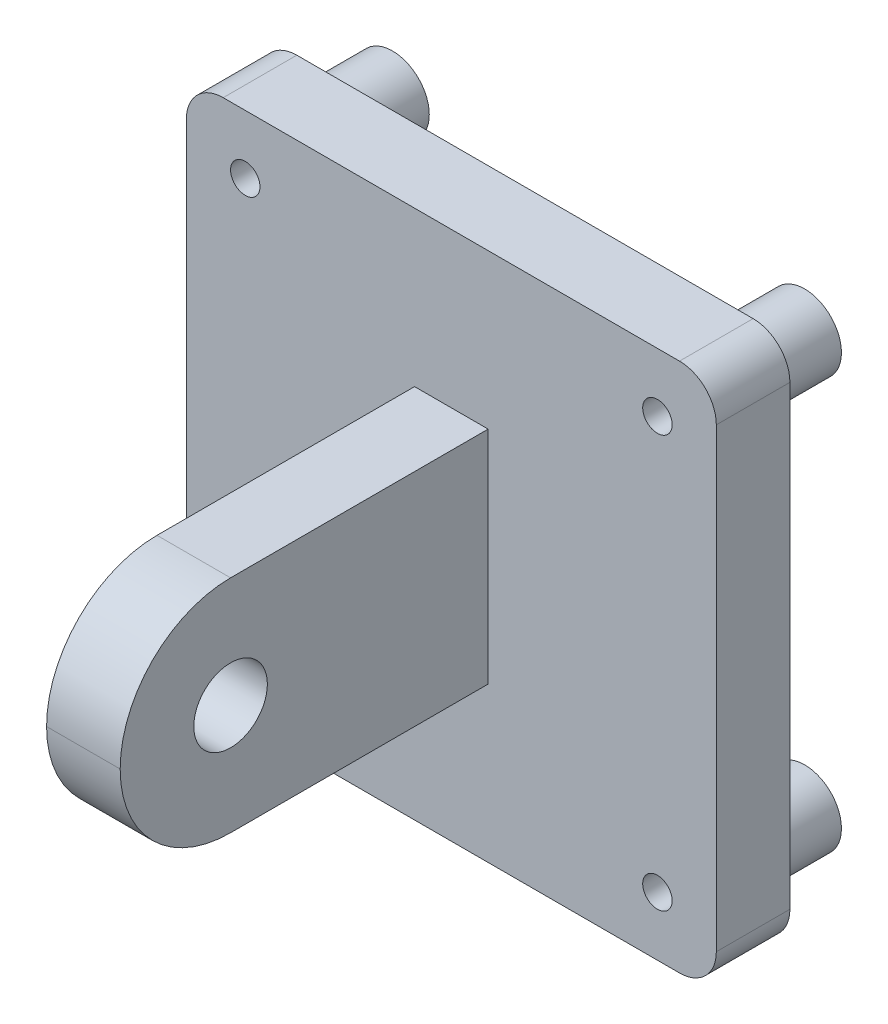
SolidWorks part; units mm, degrees
ref_plane "Front Plane" through (0, 0, 0) normal (0, 0, 1) x (1, 0, 0)
ref_plane "Top Plane" through (0, 0, 0) normal (0, 1, 0) x (1, 0, 0)
ref_plane "Right Plane" through (0, 0, 0) normal (1, 0, 0) x (0, 0, -1)
sketch "Sketch1" plane through (0, 0, 0) normal (0, 0, 1) x (1, 0, 0)
  line L1 (-18, -18) -> (18, -18)
  line L2 (-18, -18) -> (-18, 18)
  line L3 (-18, 18) -> (18, 18)
  line L4 (18, -18) -> (18, 18)
  line L5 (-14, -14) -> (14, -14)
  line L6 (-14, -14) -> (-14, 14)
  line L7 (-14, 14) -> (14, 14)
  line L8 (14, -14) -> (14, 14)
  line L9 (-14, -14) -> (14, 14) construction
  line L10 (-14, 14) -> (14, -14) construction
  circle A0 centre (-14, 14) radius 1
  circle A1 centre (14, 14) radius 1
  circle A2 centre (14, -14) radius 1
  circle A3 centre (-14, -14) radius 1
  circle A4 centre (-14, 14) radius 2.5
  circle A5 centre (14, 14) radius 2.5
  circle A6 centre (14, -14) radius 2.5
  circle A7 centre (-14, -14) radius 2.5
  point P4 (0, 0)
  dimension "D7" = 2
  dimension "D8" = 2
  dimension "D9" = 2
  dimension "D10" = 2
  dimension "D11" = 5
  dimension "D12" = 5
  dimension "D13" = 5
  dimension "D14" = 5
  dimension "D1" = 18
  dimension "D2" = 18
  dimension "D3" = 36
  dimension "D4" = 36
  dimension "D5" = 28
  dimension "D6" = 28
extrude "Boss-Extrude1" add sketch "Sketch1" against normal blind 5 contours L7 A4 L6 A0 | L6 A4 L7 A0 | L8 A5 L7 A1 | L7 A5 L8 A1 | L5 A7 L6 A3 | L6 A7 L5 A3 | L5 A6 L8 A2 | L8 A6 L5 A2 region at (-12.8177, -12.8177, 0) region at (-12.25, -14.0707, 0) region at (12.8177, -12.8177, 0) region at (12.25, -14.0707, 0) region at (-15.7178, 15.7178, 0) region at (-12.8177, 12.8177, 0) region at (12.8177, 12.8177, 0) region at (14.0707, 12.25, 0)
extrude "Boss-Extrude2" add sketch "Sketch1<3>" along normal blind 5 contours L1 L4 L3 L2 A7 L6 A4 L7 A5 L8 A6 L5 | A7 L5 A6 L8 A5 L7 A4 L6 | L6 A7 L5 A3 | L5 A7 L6 A3 | L7 A4 L6 A0 | L6 A4 L7 A0 | L8 A6 L5 A2 | L5 A6 L8 A2 | L7 A5 L8 A1 | L8 A5 L7 A1 region at (-17.4909, 0, 0) region at (-12.8177, -12.8177, 0) region at (-12.25, -14.0707, 0) region at (0, 0, 0) region at (12.8177, -12.8177, 0) region at (12.25, -14.0707, 0) region at (-15.7178, 15.7178, 0) region at (-12.8177, 12.8177, 0) region at (12.8177, 12.8177, 0) region at (14.0707, 12.25, 0)
sketch "Sketch1<3>" plane through (0, 0, 0) normal (0, 0, 1) x (1, 0, 0) same geometry as "Sketch1"
fillet "Fillet1" radius 2.5 4 edges at (18, 18, 2.5) (-18, 18, 2.5) (-18, -18, 2.5) (18, -18, 2.5)
sketch "Sketch2" plane through (0, 0, 5) normal (0, 0, 1) x (1, 0, 0)
  line L1 (-2.5, -7.5) -> (2.5, -7.5)
  line L2 (-2.5, -7.5) -> (-2.5, 7.5)
  line L3 (-2.5, 7.5) -> (2.5, 7.5)
  line L4 (2.5, -7.5) -> (2.5, 7.5)
  line L5 (-2.5, -7.5) -> (2.5, 7.5) construction
  line L6 (-2.5, 7.5) -> (2.5, -7.5) construction
  point P0 (0, 0)
  dimension "D1" = 5
  dimension "D2" = 15
extrude "Boss-Extrude3" add sketch "Sketch2" along normal blind 25
sketch "Sketch3" plane through (2.5, 0, 0) normal (1, 0, 0) x (0, 0, -1)
  line L0 (-30, -7.5) -> (-30, 7.5) construction
  line L1 (-30, 7.5) -> (-5, 7.5) construction
  circle A0 centre (-22.5, 0) radius 2.5
  dimension "D1" = 5
  dimension "D2" = 7.5
  dimension "D3" = 7.5
fillet "Fillet2" radius 7.5 2 edges at (0, -7.5, 30) (0, 7.5, 30)
extrude "Cut-Extrude1" cut sketch "Sketch3" against normal blind 5 contours A0
